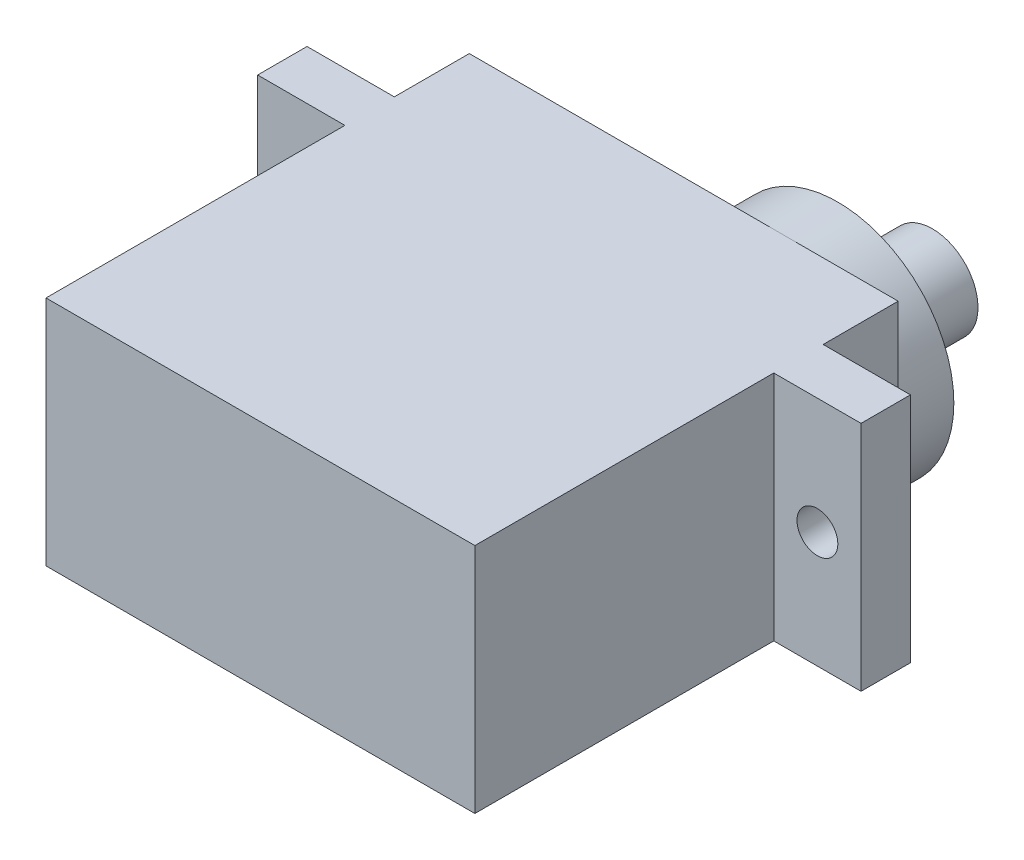
SolidWorks part; units mm, degrees
ref_plane "前视基准面" through (0, 0, 0) normal (0, 0, 1) x (1, 0, 0)
ref_plane "上视基准面" through (0, 0, 0) normal (0, 1, 0) x (1, 0, 0)
ref_plane "右视基准面" through (0, 0, 0) normal (1, 0, 0) x (0, 0, -1)
sketch "草图1" plane through (0, 0, 0) normal (0, 0, 1) x (1, 0, 0)
  line L1 (0, 0) -> (32.5, 0)
  line L2 (0, 0) -> (0, 12.5)
  line L3 (0, 12.5) -> (32.5, 12.5)
  line L4 (32.5, 0) -> (32.5, 12.5)
  line L5 (4.7, 0) -> (27.8, 0)
  line L6 (4.7, 0) -> (4.7, 12.5)
  line L7 (4.7, 12.5) -> (27.8, 12.5)
  line L8 (27.8, 0) -> (27.8, 12.5)
  circle A0 centre (21.55, 6.25) radius 6.25
  circle A1 centre (21.55, 6.25) radius 2.45
  dimension "D5" = 4.9
  dimension "D1" = 32.5
  dimension "D2" = 12.5
  dimension "D3" = 23.1
extrude "凸台-拉伸1" add sketch "草图1" along normal blind 16.1 contours A0 L3 L6 L1 | A0 L8 L7 | A0 L5 L8 | A0 A1 | A1 region at (10.7521, 6.25, 0) region at (26.404, 1.396, 0) region at (15.4768, 6.25, 0) region at (26.404, 11.104, 0) region at (21.55, 6.25, 0)
extrude "凸台-拉伸2" add sketch "草图1<3>" against normal blind 2.66 contours L1 L6 L3 L2 | L8 L1 L4 L3 | A0 L3 L6 L1 | A0 L5 L8 | A0 L8 L7 | A0 A1 | A1 region at (2.35, 6.25, 0) region at (10.7521, 6.25, 0) region at (26.404, 1.396, 0) region at (15.4768, 6.25, 0) region at (30.15, 6.25, 0) region at (26.404, 11.104, 0) region at (21.55, 6.25, 0)
sketch "草图1<3>" plane through (0, 0, 0) normal (0, 0, 1) x (1, 0, 0) same geometry as "草图1"
extrude "凸台-拉伸3" add sketch "草图1<4>" against normal blind 6.7 contours A0 L3 L6 L1 | A0 A1 | A1 | A0 L5 L8 | A0 L8 L7 region at (10.7521, 6.25, 0) region at (26.404, 1.396, 0) region at (15.4768, 6.25, 0) region at (26.404, 11.104, 0) region at (21.55, 6.25, 0)
sketch "草图1<4>" plane through (0, 0, 0) normal (0, 0, 1) x (1, 0, 0) same geometry as "草图1"
extrude "凸台-拉伸4" add sketch "草图1<5>" against normal offset from surface (9.7 mm away) 3 contours A0 A1 | A1 region at (15.4768, 6.25, 0) region at (21.55, 6.25, 0) up to face at (16.25, 6.25, -6.7) offset beyond the face yes
sketch "草图1<5>" plane through (0, 0, 0) normal (0, 0, 1) x (1, 0, 0) same geometry as "草图1"
extrude "凸台-拉伸5" add sketch "草图1<6>" against normal blind 14.8 contours A1 region at (21.55, 6.25, 0)
sketch "草图1<6>" plane through (0, 0, 0) normal (0, 0, 1) x (1, 0, 0) same geometry as "草图1"
sketch "草图2" plane through (0, 0, -2.66) normal (0, 0, -1) x (-1, 0, 0)
  line L2 (-27.8, 0) -> (-27.8, 12.5) construction
  line L3 (-32.5, 0) -> (-32.5, 12.5) construction
  circle A0 centre (-30.15, 6.25) radius 1.1
  point P6 (-28.7468, 3.0511)
  point P7 (0, 0)
  point P8 (0, 0)
  point P9 (-32.5, 6.25)
  dimension "D1" = 2.35
sketch "草图3" plane through (0, 0, -2.66) normal (0, 0, -1) x (-1, 0, 0)
  line L0 (0, 0) -> (0, 12.5) construction
  circle A0 centre (-2.1294, 6.25) radius 1.1
  point P4 (0, 6.25)
extrude "切除-拉伸1" cut sketch "草图3" against normal blind 14.8
extrude "切除-拉伸2" cut sketch "草图2" against normal blind 14.8
